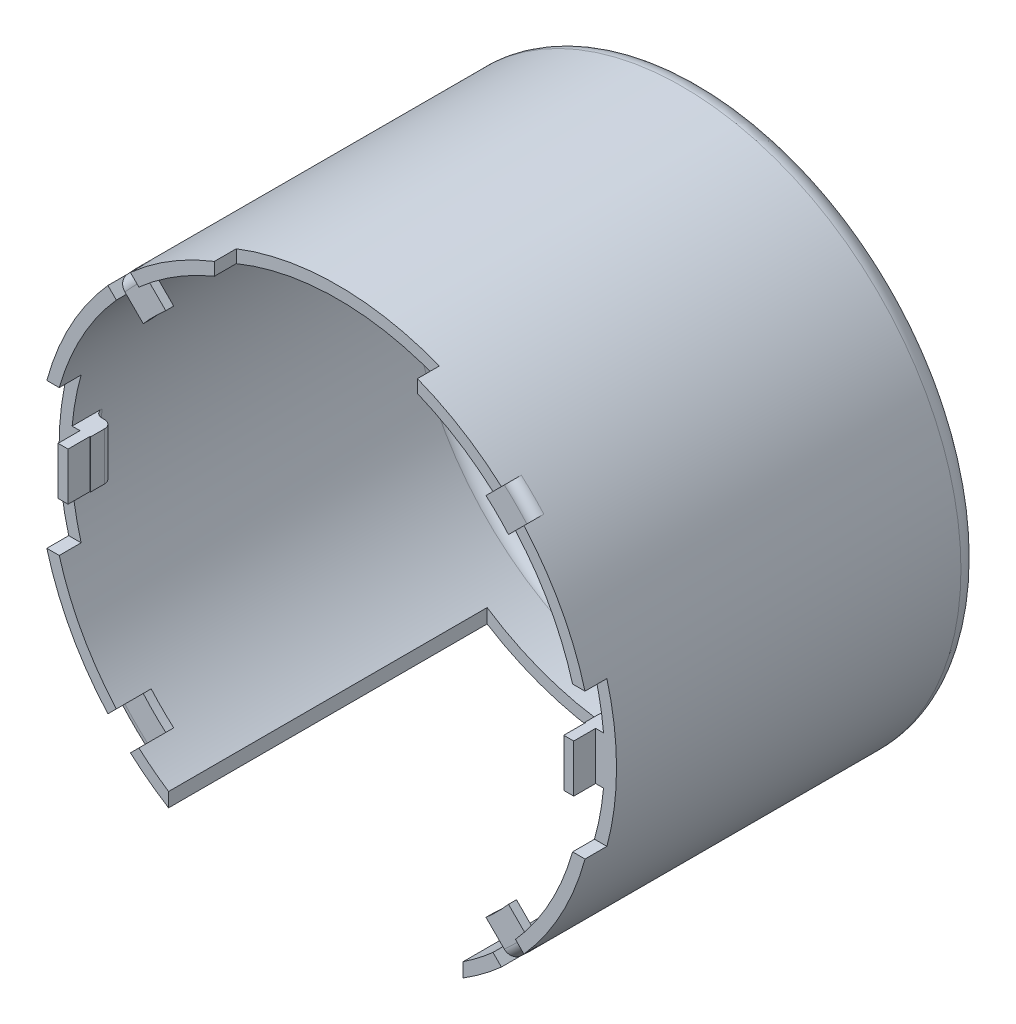
SolidWorks part; units mm, degrees
material "1023 Листовая углеродистая сталь (SS)"
ref_plane "Front Plane" through (0, 0, 0) normal (0, 0, 1) x (1, 0, 0)
ref_plane "Top Plane" through (0, 0, 0) normal (0, 1, 0) x (1, 0, 0)
ref_plane "Right Plane" through (0, 0, 0) normal (1, 0, 0) x (0, 0, -1)
sketch "Sketch1" plane through (0, 0, 0) normal (0, 0, 1) x (1, 0, 0)
  circle A0 centre (0, 0) radius 14
  dimension "D1" = 28
extrude "Extrude1" add sketch "Sketch1" along normal blind 19.4
fillet "Fillet1" radius 1 1 edges at (14, 0, 0)
sketch "Sketch2" plane through (0, 0, 0) normal (0, 1, 0) x (1, 0, 0)
  line L0 (0, -19.4) -> (0, 0) construction
  line L1 (-14, -19.4) -> (14, -19.4) construction
  line L2 (-13.4, -19.4) -> (-13.4, -1.3)
  line L3 (0, -0.6) -> (0, -20.2731)
  line L4 (-12.7, -0.6) -> (0, -0.6)
  line L5 (-13.4, -19.4) -> (-13.4, -20.2731)
  line L6 (-13.4, -20.2731) -> (0, -20.2731)
  line L7 (-14, -1) -> (-14, -19.4) construction
  line L8 (13, 0) -> (-13, 0) construction
  arc A0 (-13.4, -1.3) -> (-12.7, -0.6) centre (-12.7, -1.3) cw
  dimension "D3" = 0.7
  dimension "D1" = 0.6
  dimension "D2" = 0.6
revolve "Cut-Revolve1" cut sketch "Sketch2" angle 360 about L0
sketch "Sketch4" plane through (0, 0, 0) normal (0, 1, 0) x (1, 0, 0)
  line L0 (-14, -18.9) -> (-12.2, -18.9)
  line L1 (-14, -1) -> (-14, -19.4) construction
  line L2 (-12.2, -18.9) -> (-12.2, -18.5)
  line L3 (-12.2, -18.5) -> (-14, -18.5)
  line L4 (-14, -18.5) -> (-14, -18.9)
  line L5 (0, 0) -> (0, -21.9454) construction
  line L6 (-13.4, -19.4) -> (13.4, -19.4) construction
  dimension "D1" = 0.4
  dimension "D2" = 1.8
  dimension "D3" = 0.5
revolve "Revolve1" add sketch "Sketch4" angle 360 about L5
sketch "Sketch3" plane through (0, 0, 0) normal (0, 1, 0) x (1, 0, 0)
  line L0 (0, -19.4) -> (0, 0) construction
  line L1 (-14, -19.4) -> (14, -19.4) construction
  line L3 (-7.4, -19.4) -> (7.4, -19.4)
  line L4 (-7.4, -19.4) -> (-7.4, -3.4)
  line L5 (-7.4, -3.4) -> (7.4, -3.4)
  line L6 (7.4, -19.4) -> (7.4, -3.4)
  line L7 (-7.4, -19.4) -> (7.4, -3.4) construction
  line L8 (-7.4, -3.4) -> (7.4, -19.4) construction
  point P5 (0, -11.4)
  dimension "D1" = 16
  dimension "D2" = 14.8
extrude "Extrude2" cut sketch "Sketch3" against normal through all
sketch "Sketch5" plane through (0, 0, 19.4) normal (0, 0, 1) x (1, 0, 0)
  line L0 (0, 0) -> (0, 14) construction
  line L1 (0, 14) -> (14, 0) construction
  line L2 (14, 0) -> (0, 0) construction
  line L3 (0, 0) -> (7, 7) construction
  line L4 (7, 7) -> (10.4038, 10.4038) construction
  line L5 (7.6761, 8.8074) -> (9.636, 10.7674)
  line L6 (8.8074, 7.6761) -> (10.7674, 9.636)
  line L7 (10.7674, 9.636) -> (9.636, 10.7674)
  line L8 (7.6761, 8.8074) -> (8.8074, 7.6761)
  line L9 (8.8074, -7.6761) -> (7.6761, -8.8074)
  line L10 (7.6761, -8.8074) -> (9.636, -10.7674)
  line L11 (9.636, -10.7674) -> (10.7674, -9.636)
  line L12 (8.8074, -7.6761) -> (10.7674, -9.636)
  line L13 (-7.6761, -8.8074) -> (-8.8074, -7.6761)
  line L14 (-8.8074, -7.6761) -> (-10.7674, -9.636)
  line L15 (-10.7674, -9.636) -> (-9.636, -10.7674)
  line L16 (-7.6761, -8.8074) -> (-9.636, -10.7674)
  line L17 (-8.8074, 7.6761) -> (-7.6761, 8.8074)
  line L18 (-7.6761, 8.8074) -> (-9.636, 10.7674)
  line L19 (-9.636, 10.7674) -> (-10.7674, 9.636)
  line L20 (-8.8074, 7.6761) -> (-10.7674, 9.636)
  arc A0 (7.4, -11.8844) -> (-7.4, -11.8844) centre (0, 0) ccw construction
  point P28 (0, 0)
  dimension "D1" = 0.8
  dimension "D2" = 1.6
  dimension "D3" = 4
extrude "Extrude3" cut sketch "Sketch5" against normal blind 0.5
sketch "Sketch6" plane through (0, 0, 18.9) normal (0, 0, 1) x (1, 0, 0)
  line L0 (8.8926, 10.024) -> (7.509, 8.6404)
  line L1 (7.509, 8.6404) -> (8.6404, 7.509)
  line L2 (8.6404, 7.509) -> (10.024, 8.8926)
  line L3 (9.3176, 10.449) -> (8.8926, 10.024) construction
  line L4 (10.024, 8.8926) -> (10.449, 9.3176) construction
  line L5 (10.024, -8.8926) -> (8.6404, -7.509)
  line L6 (8.6404, -7.509) -> (7.509, -8.6404)
  line L7 (7.509, -8.6404) -> (8.8926, -10.024)
  line L8 (-8.8926, -10.024) -> (-7.509, -8.6404)
  line L9 (-7.509, -8.6404) -> (-8.6404, -7.509)
  line L10 (-8.6404, -7.509) -> (-10.024, -8.8926)
  line L11 (-10.024, 8.8926) -> (-8.6404, 7.509)
  line L12 (-8.6404, 7.509) -> (-7.509, 8.6404)
  line L13 (-7.509, 8.6404) -> (-8.8926, 10.024)
  arc A0 (8.8926, 10.024) -> (0, 13.4) centre (0, 0) ccw
  arc A1 (8.8926, 10.024) -> (-8.8926, 10.024) centre (0, 0) ccw construction
  arc A2 (10.024, 8.8926) -> (13.4, 0) centre (0, 0) cw
  arc A3 (10.024, -8.8926) -> (10.024, 8.8926) centre (0, 0) ccw construction
  arc A4 (10.024, -8.8926) -> (13.4, 0) centre (0, 0) ccw
  arc A5 (8.8926, -10.024) -> (0, -13.4) centre (0, 0) cw
  arc A6 (-8.8926, -10.024) -> (0, -13.4) centre (0, 0) ccw
  arc A7 (-10.024, -8.8926) -> (-13.4, 0) centre (0, 0) cw
  arc A8 (-10.024, 8.8926) -> (-13.4, 0) centre (0, 0) ccw
  arc A9 (-8.8926, 10.024) -> (0, 13.4) centre (0, 0) cw
  point P41 (0, 0)
  dimension "D1" = 4
extrude "Extrude4" cut sketch "Sketch6" against normal blind 2
fillet "Fillet2" radius 0.5 4 edges at (-9.8995, -9.8995, 18.9) (-9.8995, 9.8995, 18.9) (9.8995, 9.8995, 18.9) (9.8995, -9.8995, 18.9)
sketch "Sketch7" plane through (0, 0, 19.4) normal (0, 0, 1) x (1, 0, 0)
  line L1 (-5.1, 16) -> (5.1, 16)
  line L2 (-5.1, 16) -> (-5.1, 12)
  line L3 (-5.1, 12) -> (5.1, 12)
  line L4 (5.1, 16) -> (5.1, 12)
  line L5 (-5.1, 16) -> (5.1, 12) construction
  line L6 (-5.1, 12) -> (5.1, 16) construction
  arc A0 (9.3176, 10.449) -> (-9.3176, 10.449) centre (0, 0) ccw construction
  point P0 (0, 14)
  dimension "D1" = 4
  dimension "D2" = 10.2
sketch "Sketch8" plane through (0, 0, 19.4) normal (0, 0, 1) x (1, 0, 0)
  line L1 (-17.5, 3.65) -> (17.5, 3.65)
  line L2 (-17.5, 3.65) -> (-17.5, -3.65)
  line L3 (-17.5, -3.65) -> (17.5, -3.65)
  line L4 (17.5, 3.65) -> (17.5, -3.65)
  line L5 (-17.5, 3.65) -> (17.5, -3.65) construction
  line L6 (-17.5, -3.65) -> (17.5, 3.65) construction
  point P0 (0, 0)
  dimension "D1" = 7.3
  dimension "D2" = 35
extrude "Extrude6" cut sketch "Sketch8" against normal blind 1.1
extrude "Extrude5" cut sketch "Sketch7" against normal blind 1.1
sketch "Sketch10" plane through (0, 0, 18.3) normal (0, 0, 1) x (1, 0, 0)
  line L0 (0, 0) -> (0, -12.7) construction
  line L1 (13.6657, 1.2) -> (12.4157, 1.2)
  line L2 (13.6657, 1.2) -> (13.6657, -1.2)
  line L3 (13.6657, -1.2) -> (12.4157, -1.2)
  line L4 (12.4157, 1.2) -> (12.4157, -1.2)
  line L5 (13.6657, 1.2) -> (12.4157, -1.2) construction
  line L6 (13.6657, -1.2) -> (12.4157, 1.2) construction
  line L7 (-13.6657, -1.2) -> (-12.4157, -1.2)
  line L8 (-12.4157, 1.2) -> (-12.4157, -1.2)
  line L9 (-13.6657, 1.2) -> (-12.4157, 1.2)
  line L10 (-13.6657, 1.2) -> (-13.6657, -1.2)
  circle A0 centre (0, 0) radius 12.7 construction
  point P4 (13.0407, 0)
  dimension "D1" = 2.4
  dimension "D2" = 1.25
extrude "Extrude7" add sketch "Sketch10" against normal blind 1.1
sketch "Sketch9" plane through (0, 0, 18.3) normal (0, 0, -1) x (-1, 0, 0)
  line L0 (0, 0) -> (0, 14) construction
  line L1 (12.95, -1.2) -> (12.45, -1.2)
  line L2 (12.95, -1.2) -> (12.95, 1.2)
  line L3 (12.95, 1.2) -> (12.45, 1.2)
  line L4 (12.45, -1.2) -> (12.45, 1.2)
  line L5 (12.95, -1.2) -> (12.45, 1.2) construction
  line L6 (12.95, 1.2) -> (12.45, -1.2) construction
  line L7 (-12.95, 1.2) -> (-12.45, -1.2) construction
  line L8 (-12.95, -1.2) -> (-12.45, 1.2) construction
  line L9 (-12.45, -1.2) -> (-12.45, 1.2)
  line L10 (-12.95, 1.2) -> (-12.45, 1.2)
  line L11 (-12.95, -1.2) -> (-12.95, 1.2)
  line L12 (-12.95, -1.2) -> (-12.45, -1.2)
  circle A0 centre (0, 0) radius 12.7 construction
  arc A1 (5.1, 13.038) -> (-5.1, 13.038) centre (0, 0) ccw construction
  point P0 (12.7, 0)
  point P17 (-12.7, 0)
  dimension "D1" = 2.4
  dimension "D2" = 0.5
extrude "Extrude8" add sketch "Sketch9" against normal blind 1.1
fillet "Fillet3" radius 0.4 4 edges at (13.4, 0, 17.2) (-13.4, 0, 17.2) (-12.4157, 0, 17.2) (12.4157, 0, 17.2)
